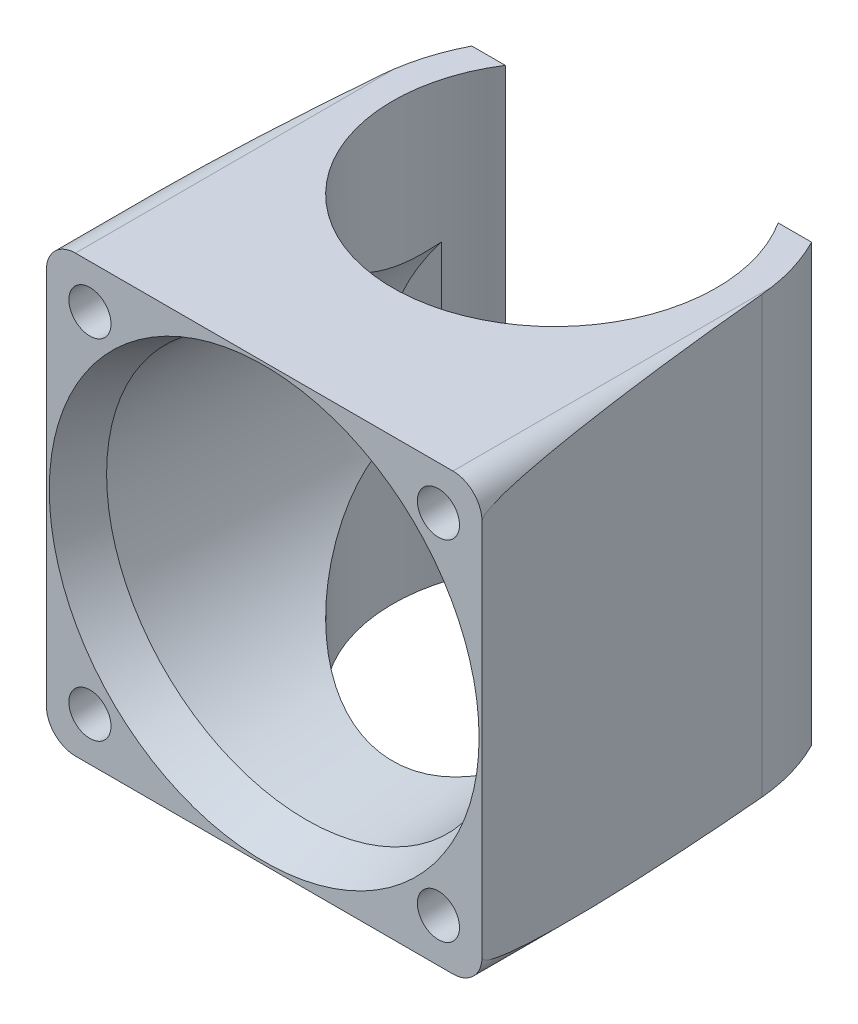
SolidWorks part; units mm, degrees
ref_plane "Alzado" through (0, 0, 0) normal (0, 0, 1) x (1, 0, 0)
ref_plane "Planta" through (0, 0, 0) normal (0, 1, 0) x (1, 0, 0)
ref_plane "Vista lateral" through (0, 0, 0) normal (1, 0, 0) x (0, 0, -1)
sketch "Croquis1" plane through (0, 0, 0) normal (0, 0, 1) x (1, 0, 0)
  line L1 (-15, -15) -> (15, -15)
  line L2 (-15, -15) -> (-15, 15)
  line L3 (-15, 15) -> (15, 15)
  line L4 (15, -15) -> (15, 15)
  line L5 (-15, -15) -> (15, 15) construction
  line L6 (-15, 15) -> (15, -15) construction
  point P0 (0, 0)
  dimension "D1" = 30
  dimension "D2" = 30
extrude "Saliente-Extruir1" add sketch "Croquis1" against normal blind 26
fillet "Redondeo1" radius 2 4 edges at (15, 15, -13) (15, -15, -13) (-15, -15, -13) (-15, 15, -13)
sketch "Croquis2" plane through (0, 0, 0) normal (0, 0, 1) x (1, 0, 0)
  line L1 (-12, -12) -> (12, -12) construction
  line L2 (-12, -12) -> (-12, 12) construction
  line L3 (-12, 12) -> (12, 12) construction
  line L4 (12, -12) -> (12, 12) construction
  line L5 (-12, -12) -> (12, 12) construction
  line L6 (-12, 12) -> (12, -12) construction
  circle A0 centre (-12, 12) radius 1.45
  circle A1 centre (12, 12) radius 1.45
  circle A2 centre (12, -12) radius 1.45
  circle A3 centre (-12, -12) radius 1.45
  point P0 (0, 0)
  dimension "D3" = 2.9
  dimension "D1" = 24
  dimension "D2" = 24
extrude "Cortar-Extruir1" cut sketch "Croquis2" against normal blind 5
sketch "Croquis3" plane through (0, 15, 0) normal (0, 1, 0) x (1, 0, 0)
  line L0 (13, 26) -> (-13, 26) construction
  line L1 (-15, 0) -> (-13.0972, 21.1768)
  line L2 (15, 0) -> (13.0972, 21.1768)
  line L3 (15, 0) -> (15, 26)
  line L4 (15, 26) -> (13, 26) construction
  line L5 (15, 26) -> (13, 26)
  line L6 (13, 26) -> (-13, 26)
  line L7 (-13, 26) -> (-15, 26) construction
  line L8 (-13, 26) -> (-15, 26)
  line L9 (-15, 0) -> (-15, 26)
  circle A0 centre (0, 20) radius 11.15
  circle A1 centre (0, 20) radius 13.15
  line M3 (13, 0) -> (13, 26)
  line M4 (13, 26) -> (-13, 26)
  line M5 (-13, 26) -> (-13, 0)
  dimension "D1" = 22.3
  dimension "D3" = 26.3
  dimension "D2" = 6
extrude "Cortar-Extruir2" cut sketch "Croquis3" against normal through all contours A1 L8 L9 L1 M5 | A1 L6 M5 | L6 A0 | A1 L2 L3 L5 M3 | A1 M3 M4 region at (-14.2491, 15, -17.1781) region at (-12.6014, 15, -24.8069) region at (0, 15, -18.2831) region at (12.6014, 15, -24.8069) region at (14.2491, 15, -17.1781)
sketch "Croquis5" plane through (0, 0, 0) normal (0, 0, 1) x (1, 0, 0)
  circle A0 centre (0, 0) radius 14
  dimension "D1" = 28
extrude "Cortar-Extruir3" cut sketch "Croquis5" against normal up to vertex (21.1768 mm away) draft 5 up to point (13.0972, 14.9976, -21.1768)
chamfer "Chaflán1" distance 2 angle 27 2 edges at (11.0877, 0, -21.1768) (-11.0877, 0, -21.1768)
chamfer "Chaflán2" distance 0.8 angle 70 1 edges at (14, 0, 0) first distance on face at (14, 0, 0)
